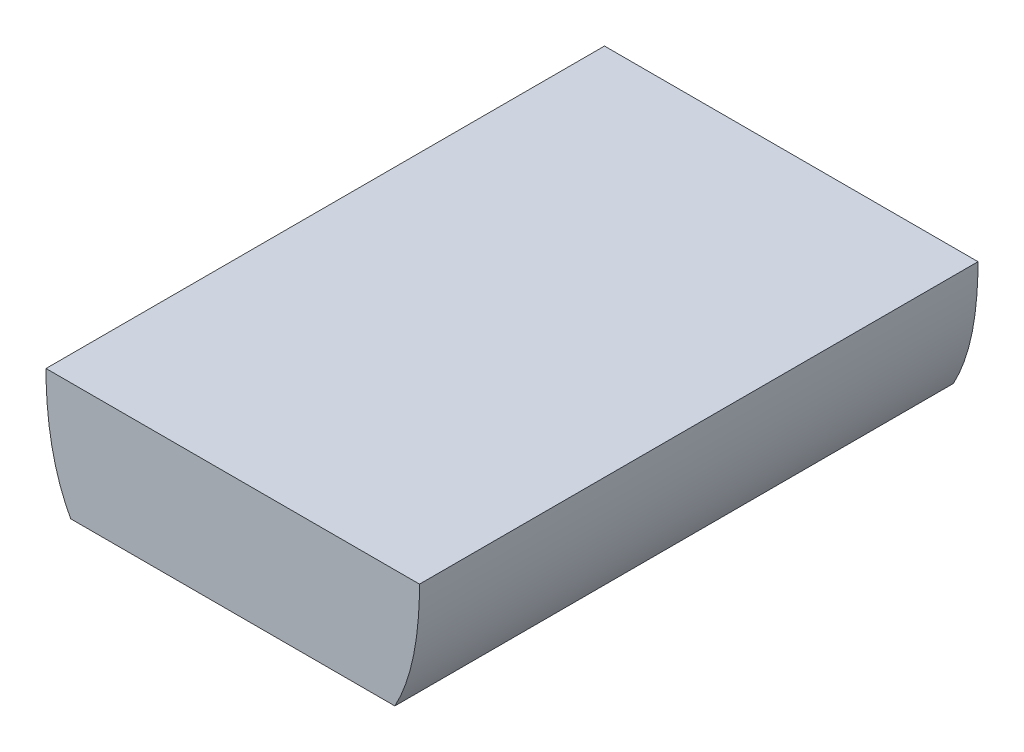
SolidWorks part; units mm, degrees
ref_plane "Front Plane" through (0, 0, 0) normal (0, 0, 1) x (1, 0, 0)
ref_plane "Top Plane" through (0, 0, 0) normal (0, 1, 0) x (1, 0, 0)
ref_plane "Right Plane" through (0, 0, 0) normal (1, 0, 0) x (0, 0, -1)
sketch "Sketch1" plane through (0, 0, 0) normal (0, 0, 1) x (1, 0, 0)
  line L0 (0, 0) -> (0, 317.813) construction
  line L2 (-302.357, 317.813) -> (302.357, 317.813)
  conic Q0 (0, 0) -> (302.357, 317.813) control (302.357, -0.0664) rho 0.504796
  conic Q1 (0, 0) -> (-302.357, 317.813) control (-302.357, -0.0664) rho 0.504796
extrude "Boss-Extrude1" add sketch "Sketch1" against normal blind 452.12 and the other way blind 452.12 contours Q0 L2 Q1
sketch "Sketch3" plane through (0, 0, 0) normal (0, 0, 1) x (1, 0, 0)
  line L0 (302.357, 0) -> (-302.357, 0)
  line L1 (302.357, 0) -> (302.357, 127)
  line L2 (302.357, 127) -> (-302.357, 127)
  line L3 (-302.357, 0) -> (-302.357, 127)
extrude "Boss-Extrude3" add sketch "Sketch3" along normal mid plane 1270 separate body
combine bodies "Combine2" operation type subtract main body 103 bodies to subtract 105
